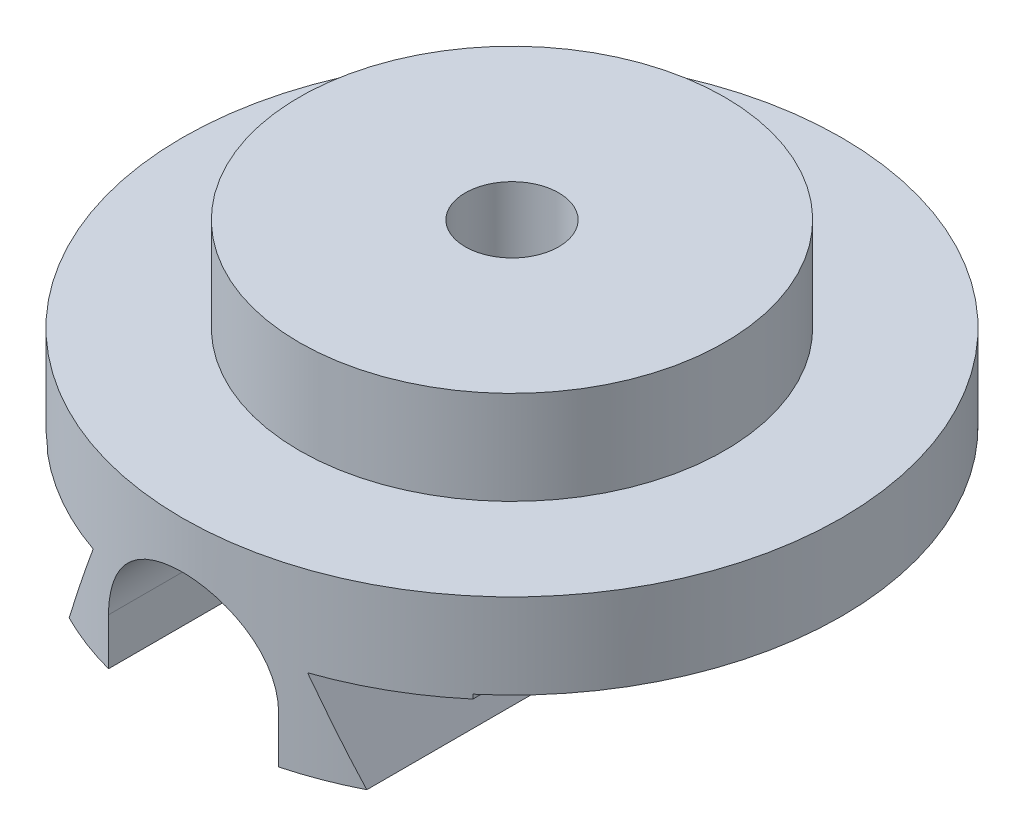
SolidWorks part; units mm, degrees
material "201 Annealed Stainless Steel (SS)"
ref_plane "Front Plane" through (0, 0, 0) normal (0, 0, 1) x (1, 0, 0)
ref_plane "Top Plane" through (0, 0, 0) normal (0, 1, 0) x (1, 0, 0)
ref_plane "Right Plane" through (0, 0, 0) normal (1, 0, 0) x (0, 0, -1)
sketch "Sketch1" plane through (0, 0, 0) normal (0, 0, 1) x (1, 0, 0)
  line L0 (35, 0) -> (-35, 0)
  line L1 (-35, 0) -> (-25.2075, 21)
  line L2 (-25.2075, 21) -> (-50, 21)
  line L3 (-50, 21) -> (-50, 22)
  line L4 (-50, 22) -> (-77.5, 22)
  line L5 (-77.5, 22) -> (-77.5, 42)
  line L6 (-77.5, 42) -> (-50, 42)
  line L7 (-50, 42) -> (-50, 64)
  line L8 (-50, 64) -> (50, 64)
  line L9 (50, 64) -> (50, 42)
  line L10 (50, 42) -> (77.5, 42)
  line L11 (77.5, 42) -> (77.5, 22)
  line L12 (77.5, 22) -> (50, 22)
  line L13 (50, 22) -> (50, 21)
  line L14 (50, 21) -> (25.2075, 21)
  line L15 (25.2075, 21) -> (35, 0)
  line L16 (0, 0) -> (0, 64) construction
  line L17 (-50, 42) -> (50, 42)
  line L18 (-20, 0) -> (-20, 11)
  line L19 (20, 11) -> (20, 0)
  line L20 (-14, 0) -> (-14, 11)
  line L21 (14, 11) -> (14, 0)
  arc A0 (-20, 11) -> (20, 11) centre (0, 11) cw
  circle A1 centre (0, 11) radius 8
  arc A2 (-14, 11) -> (14, 11) centre (0, 11) cw
  dimension "D1" = 40
  dimension "D9" = 16
  dimension "D2" = 70
  dimension "D3" = 155
  dimension "D4" = 100
  dimension "D5" = 65
  dimension "D6" = 65
  dimension "D7" = 11
  dimension "D8" = 35
  dimension "D11" = 100
  dimension "D12" = 1
  dimension "D13" = 22
  dimension "D14" = 42
  dimension "D15" = 64
  dimension "D10" = 6
extrude "Boss-Extrude1" add sketch "Sketch1" along normal mid plane 155 contours L16 A0 L19 L0 L15 L14 L13 L12 L11 L10 L17 | A0 L16 L17 L6 L5 L4 L3 L2 L1 L0 L18 | A2 L16 A0 L18 L0 L20 | L16 A2 L21 L0 L19 A0 | L0 L16 A1 A2 L20 | L16 L0 L21 A2 A1 region at (38.8954, 29.2226, 0) region at (12.7044, 17.14, 0) region at (7, 0.2865, 0) region at (-7, 0.2865, 0) region at (-38.8954, 29.2226, 0) region at (-12.7044, 17.14, 0)
revolve "Revolve1" add sketch "Sketch1<3>" angle 360 about L16 region at (-25, 53, 0)
sketch "Sketch1<3>" plane through (0, 0, 0) normal (0, 0, 1) x (1, 0, 0) same geometry as "Sketch1"
extrude "Cut-Extrude1" cut sketch "Sketch1<4>" against normal blind 39.5 from offset 77.5 contours L16 A2 L21 L0 L19 A0 | A2 L16 A0 L18 L0 L20 | L0 L16 A1 A2 L20 | L16 L0 L21 A2 A1 region at (12.7044, 17.14, 0) region at (7, 0.2865, 0) region at (-7, 0.2865, 0) region at (-12.7044, 17.14, 0)
sketch "Sketch1<4>" plane through (0, 0, 0) normal (0, 0, 1) x (1, 0, 0) same geometry as "Sketch1"
extrude "Cut-Extrude2" cut sketch "Sketch1<5>" against normal blind 77.5 contours L0 L16 A1 A2 L20 | L16 L0 L21 A2 A1 region at (7, 0.2865, 0) region at (-7, 0.2865, 0)
sketch "Sketch1<5>" plane through (0, 0, 0) normal (0, 0, 1) x (1, 0, 0) same geometry as "Sketch1"
sketch "Sketch2" plane through (0, 64, 0) normal (0, 1, 0) x (1, 0, 0)
  circle A0 centre (0, 0) radius 77.5
  dimension "D1" = 155
extrude "Cut-Extrude4" cut sketch "Sketch2" against normal blind 77.5 flip side to cut contours A0
sketch "Sketch4" plane through (0, 64, 0) normal (0, 1, 0) x (1, 0, 0)
  circle A0 centre (0, 0) radius 11
  dimension "D1" = 22
extrude "Cut-Extrude5" cut sketch "Sketch4" against normal blind 77.5
sketch "Sketch5" plane through (0, 0, 0) normal (0, -1, 0) x (1, 0, 0)
  circle A0 centre (0, 0) radius 22.5
  dimension "D1" = 45
extrude "Cut-Extrude6" cut sketch "Sketch5" against normal blind 42
